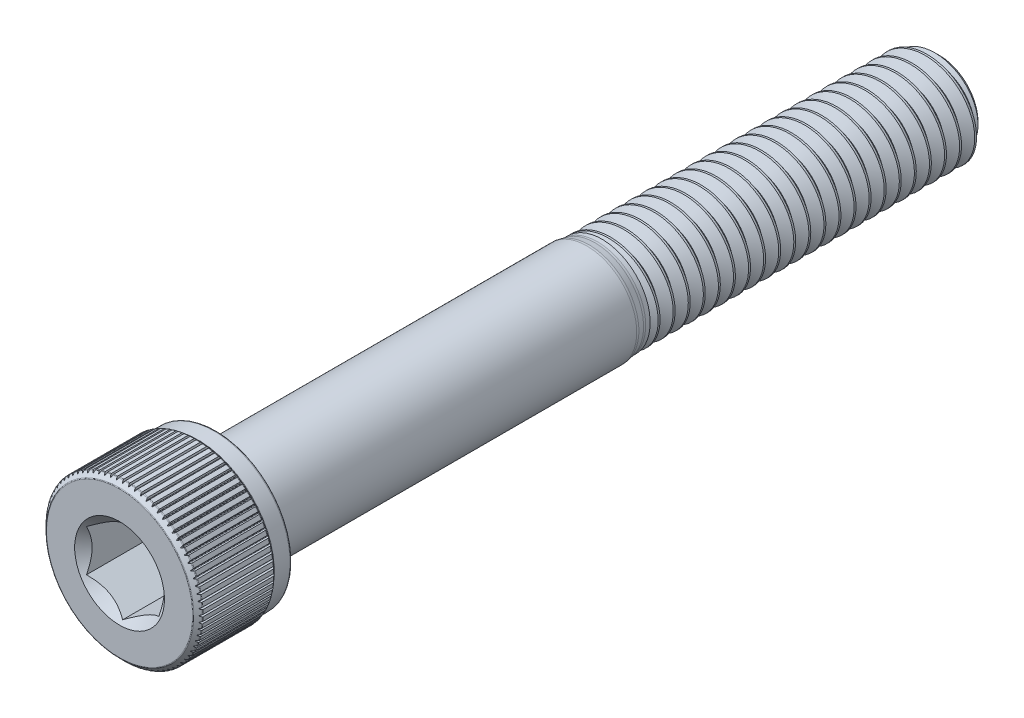
SolidWorks part; units mm, degrees
ref_plane "Front Plane" through (0, 0, 0) normal (0, 0, 1) x (1, 0, 0)
ref_plane "Top Plane" through (0, 0, 0) normal (0, 1, 0) x (1, 0, 0)
ref_plane "Right Plane" through (0, 0, 0) normal (1, 0, 0) x (0, 0, -1)
sketch "Sketch1" plane through (0, 0, 0) normal (1, 0, 0) x (0, 0, -1)
  line L0 (-34, 0) -> (34, 0) construction
  line L1 (34, 0) -> (34, 3.1881) construction
  line L2 (34, 3.1881) -> (33.1881, 4) construction
  line L3 (33.1881, 4) -> (33.0625, 4) construction
  line L4 (33.0625, 4) -> (-26, 4) construction
  line L5 (-26, 4) -> (-26, 6.5) construction
  line L6 (-26, 6.5) -> (-34, 6.5) construction
  line L7 (-34, 6.5) -> (-34, 0) construction
  line L8 (34, 3.1881) -> (34, 4) construction
  line L9 (33.9219, 4.1353) -> (34.5469, 3.0528) construction
  line L10 (34.5469, 3.0528) -> (35.1719, 4.1353) construction
  line L11 (35.1719, 4.1353) -> (33.9219, 4.1353) construction
  line L12 (34.5469, 4.1353) -> (34.5469, 4) construction
  line L13 (34.5469, 3.0528) -> (34.5469, 3.1881) construction
  line L14 (34.4688, 3.1881) -> (34.625, 3.1881) construction
  line L15 (34, 4) -> (35.0938, 4) construction
  line L16 (33.9609, 4.0677) -> (35.1328, 4.0677) construction
  line L17 (34, 0) -> (34, -4) construction
  line L18 (-26.4, 6.5) -> (-26, 6.1) construction
  line L19 (-33.6, 6.5) -> (-34, 6.1) construction
  line L20 (-26, 4) -> (-26, 0) construction
  line L21 (-26, 2) -> (-6, 2) construction
  line L22 (-6, 2) -> (14, 2) construction
  line L23 (14, 2) -> (34, 2) construction
  line L24 (-6, 2) -> (-6, 4) construction
  line L25 (-6, 4) -> (-6, 6.5) construction
  line L26 (14, 2) -> (14, 6.5) construction
  point P0 (-34, 3)
  point P3 (30.875, 4)
  point P4 (0, 0)
  point P18 (14, 4)
  point P22 (34.5469, 3.1881)
  point P24 (33.0625, 4)
  point P25 (34.5469, 4)
  point P28 (34.5469, 4.0677)
  point P29 (30.875, -4)
  point P30 (-6, 4)
  point P31 (-30, 6.5)
  point P37 (-27.4, 6.5)
  point P38 (-33.4, 6.5)
  point P45 (-6, 2)
  point P46 (14, 2)
  point P49 (6, 4)
  dimension "D1" = 45
  dimension "D2" = 0.1562
  dimension "D7" = 0.4
  dimension "D8" = 0.4
  dimension "D9" = 0.4
  dimension "D10" = 0.2
  dimension "D11" = 1
  dimension "Drive Size" = 6
  dimension "Head Diameter" = 13
  dimension "Head Height" = 8
  dimension "Thread Pitch" = 1.25
  dimension "Thread Dia" = 8
  dimension "Length" = 60
  dimension "D12" = 0.9375
  dimension "D4" = 3.125
  dimension "Minimum Thread Length" = 28
sketch "Sketch2" plane through (0, 0, 0) normal (1, 0, 0) x (0, 0, -1)
  line L0 (-34, 0) -> (-34, 6.0586)
  line L1 (-33.5586, 6.5) -> (-27.7414, 6.5)
  line L2 (-26, 6.1375) -> (-26, 4.5353)
  line L4 (33.1881, 4) -> (34, 3.1881)
  line L5 (34, 3.1881) -> (34, 0)
  line L6 (-26, 6.5) -> (-34, 6.5) construction
  line L7 (34, 0) -> (-34, 0)
  line L8 (-33.6, 6.5) -> (-34, 6.1) construction
  line L10 (-33.6293, 6.4707) -> (-33.9707, 6.1293)
  line L12 (-27.4586, 6.3) -> (-26.1625, 6.3)
  line L14 (-26.4, 6.5) -> (-26, 6.1) construction
  line L15 (-27.6707, 6.4707) -> (-27.5293, 6.3293)
  line L17 (-26, 4) -> (-26, 6.5) construction
  line L18 (-25.6, 4.1353) -> (4.7525, 4.1353)
  line L19 (5.6297, 4) -> (33.1881, 4)
  line L20 (33.0625, 4) -> (-26, 4) construction
  line L21 (4.9476, 4.1161) -> (5.4347, 4.0192)
  line L22 (35.1719, 4.1353) -> (33.9219, 4.1353) construction
  arc A0 (-26.1625, 6.3) -> (-26, 6.1375) centre (-26.1625, 6.1375) cw
  arc A1 (-26, 4.5353) -> (-25.6, 4.1353) centre (-25.6, 4.5353) ccw
  arc A2 (4.7525, 4.1353) -> (4.9476, 4.1161) centre (4.7525, 3.1353) cw
  arc A3 (5.4347, 4.0192) -> (5.6297, 4) centre (5.6297, 5) ccw
  arc A4 (-33.6293, 6.4707) -> (-33.5586, 6.5) centre (-33.5586, 6.4) cw
  arc A5 (-33.9707, 6.1293) -> (-34, 6.0586) centre (-33.9, 6.0586) ccw
  arc A6 (-27.6707, 6.4707) -> (-27.7414, 6.5) centre (-27.7414, 6.4) ccw
  arc A7 (-27.5293, 6.3293) -> (-27.4586, 6.3) centre (-27.4586, 6.4) ccw
  point P22 (-26.2, 6.3)
  point P39 (5.5313, 4)
  point P47 (-27.5, 6.3)
  dimension "D2" = 0.1625
  dimension "D3" = 0.4
  dimension "D6" = 1
  dimension "D7" = 0.1
  dimension "D1" = 1.5
  dimension "D4" = 11.25
  dimension "D5" = 0.4688
  dimension "D8" = 30.3525
revolve "Revolve1" add sketch "Sketch2" angle 360 about L7
sketch "Sketch3" plane through (0, 0, 34) normal (0, 0, 1) x (1, 0, 0)
  line L1 (3, -1.7321) -> (3, 1.7321)
  line L2 (3, 1.7321) -> (0, 3.4641)
  line L3 (0, 3.4641) -> (-3, 1.7321)
  line L4 (-3, 1.7321) -> (-3, -1.7321)
  line L5 (-3, -1.7321) -> (0, -3.4641)
  line L6 (0, -3.4641) -> (3, -1.7321)
  circle A0 centre (0, 0) radius 3 construction
  circle A1 centre (0, 0) radius 6.5 construction
  circle A2 centre (0, 0) radius 6.5 construction
  circle A3 centre (0, 0) radius 3.4641 construction
  dimension "D1" = 6.9282
extrude "Cut-Extrude1" cut sketch "Sketch3" against normal offset from surface (7 mm away) 1 up to face at (-6.1375, 0, 26)
sketch "Sketch4" plane through (0, 0, 34) normal (0, 0, 1) x (1, 0, 0)
  circle A0 centre (0, 0) radius 3.7239
  dimension "D1" = 7.4478
extrude "Cut-Extrude2" cut sketch "Sketch4" against normal up to vertex (4 mm away) draft 45 up to point (0, 6.5, 30)
sketch "Sketch11" plane through (0, 0, 0) normal (1, 0, 0) x (0, 0, -1)
  line L0 (-34, 0) -> (34, 0) construction
  line L1 (-34, 0) -> (34, 0) construction
  line L2 (-0.9386, -4) -> (-0.9386, 4) construction
  line L3 (33.0625, 4) -> (-26, 4) construction
  line L4 (-18.4119, -4) -> (-18.4119, 4) construction
  line L5 (4.7525, 4.1353) -> (4.7525, -4.1353) construction
  point P7 (-0.9386, 0)
  point P10 (-18.4119, 0)
  dimension "D1" = 7.5881
  dimension "D2" = 5.6911
sketch "Sketch6" plane through (0, 0, -34) normal (0, 0, -1) x (-1, 0, 0)
  circle A0 centre (0, 0) radius 4
curve "Helix/Spiral1" pitch 1.25 height 29.25 radius 4 centre (0, 0, -34) axis (0, 0, 1) start towards (0, 1, 0)
sketch "Sketch10" plane through (0, 0, 0) normal (1, 0, 0) x (0, 0, -1)
  line L0 (6, -4) -> (6, 4)
  line L2 (-34, 0) -> (34, 0) construction
  point P3 (6, 0)
split "Split1" trim tools "Sketch10" bodies to split 106 resulting bodies 114 115
sketch "Sketch7" plane through (0, 0, 0) normal (1, 0, 0) x (0, 0, -1)
  line L0 (33.9609, 4.0677) -> (35.1328, 4.0677)
  line L1 (35.1328, 4.0677) -> (34.625, 3.1881)
  line L2 (34.625, 3.1881) -> (34.4688, 3.1881)
  line L3 (34.4688, 3.1881) -> (33.9609, 4.0677)
sweep "Cut-Sweep1" cut profiles "Sketch7" path "Helix/Spiral1" align with end faces yes
sketch "Sketch8" plane through (0, 0, 0) normal (1, 0, 0) x (0, 0, -1)
  line L0 (-26, 0) -> (-26, 4)
  line L2 (-26, 4) -> (6, 4)
  line L4 (6, 4) -> (8.3094, 0)
  line L5 (8.3094, 0) -> (-26, 0)
  line L6 (33.0625, 4) -> (-26, 4) construction
  line L7 (-34, 0) -> (34, 0) construction
  dimension "D1" = 60
  dimension "D2" = 28
revolve "Revolve2" add sketch "Sketch8" angle 360 about L5
sketch "Sketch9" plane through (0, 0, 34) normal (0, 0, 1) x (1, 0, 0)
  line L0 (-0.0297, 6.3662) -> (-0.1625, 6.6628)
  line L1 (-0.1625, 6.6628) -> (0.1625, 6.6628)
  line L2 (0.1625, 6.6628) -> (0.0297, 6.3662)
  line L3 (0, 6.5) -> (0, 6.1) construction
  line L4 (0, 0) -> (-0.1625, 6.6628) construction
  line L5 (0.1625, 6.6628) -> (0, 0) construction
  circle A0 centre (0, 0) radius 6.3 construction
  arc A4 (-0.0297, 6.3662) -> (0.0297, 6.3662) centre (0, 6.3795) ccw
  point P10 (0, 6.3)
  point P19 (0, 6.3)
  dimension "D2" = 0.0325
  dimension "D1" = 0.325
  dimension "D3" = 2.794
extrude "Cut-Extrude3" cut sketch "Sketch9" against normal through all
pattern_circular "CirPattern1" count 80 over 360 about axis through (0, 0, 33.5586) along (0, 0, -1) of "Cut-Extrude3"
equation "\"D2@Sketch1\" = \"Thread Pitch@Sketch1\" / 8"
equation "\"D4@Helix/Spiral1\" = \"Thread Pitch@Sketch1\""
equation "\"D7@Sketch1\" = \"Head Height@Sketch1\" * .05"
equation "\"D8@Sketch1\"=\"D7@Sketch1\""
equation "\"D9@Sketch1\"=\"D7@Sketch1\""
equation "\"D10@Sketch1\"=\"D7@Sketch1\"/2"
equation "\"D11@Sketch1\"=\"D10@Sketch1\"*5"
equation "\"D4@Sketch1\"=\"Thread Pitch@Sketch1\"*2.5"
equation "\"D12@Sketch1\"=\"Thread Pitch@Sketch1\"*.75"
equation "\"D3@Helix/Spiral1\"=\"Minimum Thread Length@Sketch1\"+\"Thread Pitch@Sketch1\""
equation "\"D2@Sketch8\"=\"Minimum Thread Length@Sketch1\""
equation "\"D1@Sketch2\"=\"Head Height@Sketch1\"*0.1875"
equation "\"D2@Sketch2\"=\"Head Diameter@Sketch1\"*0.0125"
equation "\"D3@Sketch2\"=\"Thread Dia@Sketch1\"*0.05"
equation "\"D1@Sketch9\"=\"Head Diameter@Sketch1\"*0.025"
equation "\"D2@Sketch9\"=\"D1@Sketch9\"*0.1"
equation "\"D1@CirPattern1\"=int ((360/\"D3@Sketch9\")*0.625)"
equation "\"D5@Sketch2\"=\"D12@Sketch1\"*0.5"
equation "\"D6@Sketch2\"=\"Thread Dia@Sketch1\"*0.125"
equation "\"D7@Sketch2\"=\"D8@Sketch1\"*0.25"
equation "\"D1@Sketch11\"=\"D8@Sketch2\"*0.25"
equation "\"D2@Sketch11\"=\"D8@Sketch2\"*0.1875"
equation "\"D1@Sketch4\"=\"D1@Sketch3\"*1.075"
